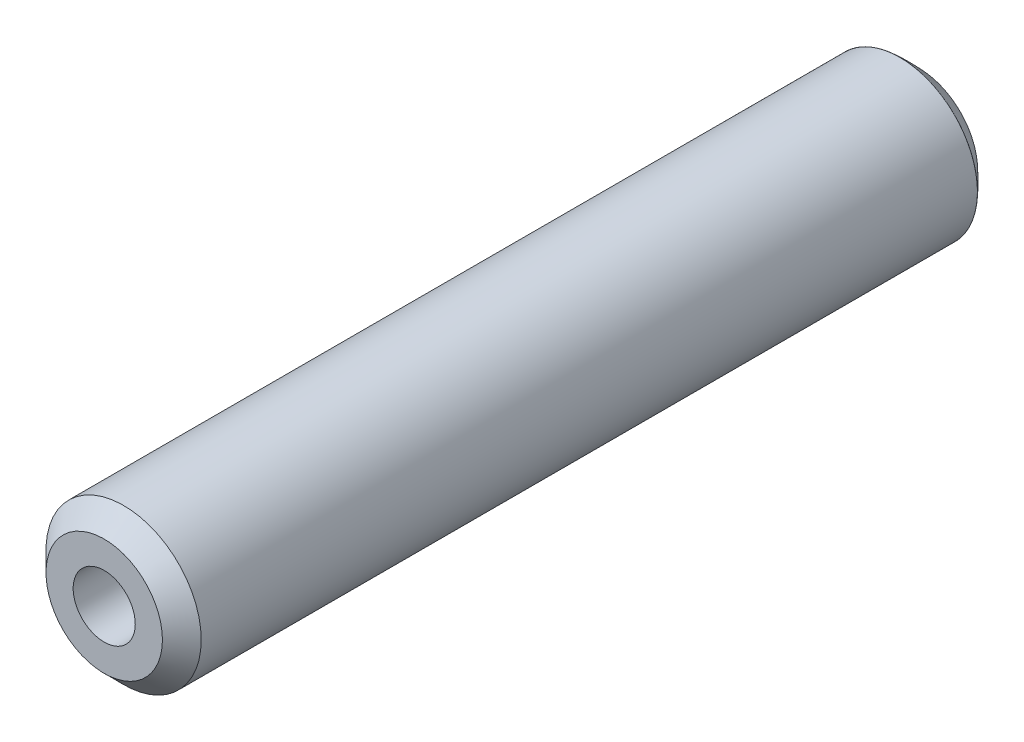
SolidWorks part; units mm, degrees
material "2A12"
ref_plane "前视基准面" through (0, 0, 0) normal (0, 0, 1) x (1, 0, 0)
ref_plane "上视基准面" through (0, 0, 0) normal (0, 1, 0) x (1, 0, 0)
ref_plane "右视基准面" through (0, 0, 0) normal (1, 0, 0) x (0, 0, -1)
sketch "草图2" plane through (0, 0, 0) normal (0, 0, 1) x (1, 0, 0)
  line L0 (0, 19.5) -> (0, -19.5) construction
  line L1 (-19, 19.5) -> (19, 19.5)
  line L2 (-19, 19.5) -> (-19, -19.5)
  line L3 (-19, -19.5) -> (19, -19.5)
  line L4 (19, 19.5) -> (19, -19.5)
  dimension "D1" = 38
  dimension "D2" = 39
extrude "拉伸1" add sketch "草图2" along normal blind 2
sketch "草图3" plane through (0, 0, 2) normal (0, 0, 1) x (1, 0, 0)
  line L0 (-14, 16.5) -> (-14, -16.5) construction
  line L1 (0, 0) -> (-14, 0) construction
  line L2 (-19, 19.5) -> (-19, -19.5) construction
  circle A0 centre (-14, 16.5) radius 1.75
  circle A1 centre (-14, -16.5) radius 1.75
  dimension "D2" = 3.5
  dimension "D1" = 33
  dimension "D3" = 5
chamfer "倒角2" [suppressed] distance 22 angle 30
chamfer "倒角3" distance 1 angle 45 2 edges at (-19, -19.5, 1) (-19, 19.5, 1)
sketch "草图4" plane through (0, 0, 2) normal (0, 0, 1) x (1, 0, 0)
  line L0 (8.205, 5.2066) -> (-4.205, -5.2066) construction
  line L1 (2, 0) -> (2, 7.25) construction
  line L2 (-3.5538, 4.6602) -> (7.5538, -4.6602) construction
  line L3 (2, 0) -> (19, 0) construction
  line L4 (-19, 18.5) -> (-19, -18.5) construction
  line L5 (19, -19.5) -> (19, 19.5) construction
  circle A0 centre (2, 0) radius 8.1 construction
  circle A1 centre (2, 0) radius 7.25 construction
  dimension "D1" = 16.2
  dimension "D2" = 14.5
  dimension "D3" = 50
  dimension "D4" = 50
  dimension "D5" = 21
hole_wizard "M1.6 螺纹孔1" [suppressed] positions "3D草图2" profile "草图6" tap size "M1.6" standard "GB"
sketch3d "3D草图2"
  point P3 (13.145, 5.2066, 2)
  point P6 (12.4938, -4.6602, 2)
  point P9 (0.735, -5.2066, 2)
  point P12 (1.3862, 4.6602, 2)
sketch "草图6" plane through (13.145, 5.2066, 2) normal (1, 0, 0) x (0, -1, 0)
  line L0 (0, 0) -> (0, 4.6255)
  line L1 (0, 4.6255) -> (0.625, 4.25)
  line L2 (0.625, 4.25) -> (0.625, 0)
  line L5 (0.625, 0) -> (0, 0)
  line L10 (0, 4.6255) -> (-0.625, 4.25) construction
  line L11 (0, -6.35) -> (0, 107.95) construction
  dimension "螺纹孔钻头直径" = 1.25
  dimension "螺纹孔钻头深度" = 4.25
  dimension "导头角度" = 118
cosmetic thread "Hole Thread1" [suppressed] parameters "D1"=2, "D2"=1.6
cosmetic thread "Hole Thread2" [suppressed] parameters "D1"=2, "D2"=1.6
cosmetic thread "Hole Thread3" [suppressed] parameters "D1"=2, "D2"=1.6
cosmetic thread "Hole Thread4" [suppressed] parameters "D1"=2, "D2"=1.6
sketch "草图7" plane through (0, 0, 2) normal (0, 0, 1) x (1, 0, 0)
  line L0 (-2.25, 0) -> (2, 0) construction
  circle A0 centre (2, 0) radius 4.25
  dimension "D1" = 8.5
extrude "拉伸3" cut sketch "草图7" against normal blind 10
sketch "草图8" plane through (0, 0, 2) normal (0, 0, 1) x (1, 0, 0)
  line L0 (19, 19.5) -> (-18, 19.5) construction
  line L1 (-17, 19.5) -> (-19, 19.5)
  line L2 (-17, 19.5) -> (-17, -19.5)
  line L3 (-17, -19.5) -> (-19, -19.5)
  line L4 (-19, 19.5) -> (-19, -19.5)
  line L5 (-18, -19.5) -> (19, -19.5) construction
  line L6 (-19, 18.5) -> (-19, -18.5) construction
  dimension "D1" = 2
extrude "拉伸4" cut sketch "草图8" against normal blind 10
chamfer "倒角4" [suppressed] distance 1.5 angle 45
fillet "圆角3" radius 2 2 edges at (-17, -19.5, 1) (-17, 19.5, 1)
sketch "Sketch1" plane through (0, 0, 2) normal (0, 0, 1) x (1, 0, 0)
  line L0 (2, 0) -> (19, 0)
  line L1 (19, -19.5) -> (19, 19.5) construction
  line L2 (7.7569, 7.557) -> (-3.7569, -7.557)
  line L3 (-3.7569, 7.557) -> (7.7569, -7.557)
  dimension "D1" = 52.7
  dimension "D2" = 19
  dimension "D3" = 52.7
hole_wizard "M2.5 Tapped Hole1" [suppressed] positions "3DSketch1" profile "Sketch2" tap size "M2.5" standard "GB"
sketch3d "3DSketch1"
  point P0 (-3.7569, -7.557, 2)
  point P3 (7.7569, 7.557, 2)
  point P7 (-3.7569, 7.557, 2)
  point P10 (7.7569, -7.557, 2)
sketch "Sketch2" plane through (-3.7569, -7.557, 2) normal (1, 0, 0) x (0, -1, 0)
  line L0 (0, 0) -> (0, 7.8659)
  line L1 (0, 7.8659) -> (1.025, 7.25)
  line L2 (1.025, 7.25) -> (1.025, 0)
  line L5 (1.025, 0) -> (0, 0)
  line L10 (0, 7.8659) -> (-1.025, 7.25) construction
  line L11 (0, -6.35) -> (0, 107.95) construction
  dimension "Tap Drill Dia." = 2.05
  dimension "Tap Drill Depth" = 7.25
  dimension "Drill Angle" = 118
cosmetic thread "Hole Thread5" [suppressed] parameters "D1"=2, "D2"=2.5
cosmetic thread "Hole Thread6" [suppressed] parameters "D1"=2, "D2"=2.5
cosmetic thread "Hole Thread7" [suppressed] parameters "D1"=2, "D2"=2.5
cosmetic thread "Hole Thread8" [suppressed] parameters "D1"=2, "D2"=2.5
fillet "Fillet1" [suppressed] radius 3
sketch "Sketch3" [suppressed] plane through (0, 0, 2) normal (0, 0, 1) x (1, 0, 0)
  line L1 (19, 19.5) -> (15, 19.5)
  line L2 (19, 19.5) -> (19, 9.5)
  line L3 (19, 9.5) -> (15, 9.5)
  line L4 (15, 19.5) -> (15, 9.5)
  line L5 (19, -19.5) -> (15, -19.5)
  line L6 (19, -19.5) -> (19, -9.5)
  line L7 (19, -9.5) -> (15, -9.5)
  line L8 (15, -19.5) -> (15, -9.5)
  dimension "D1" = 10
  dimension "D2" = 4
extrude "Extrude1" [suppressed] cut sketch "Sketch3" against normal blind 10
chamfer "Chamfer1" [suppressed] distance 5 angle 45
fillet "Fillet2" [suppressed] radius 2.5
fillet "Fillet3" [suppressed] radius 2.5
fillet "Fillet4" [suppressed] radius 2.5
chamfer "Chamfer2" [suppressed] distance 4 angle 45
sketch "草图9" plane through (0, 0, 2) normal (0, 0, 1) x (1, 0, 0)
  circle A0 centre (-15, 17.5) radius 2
  arc A2 (-15, 19.5) -> (-17, 17.5) centre (-15, 17.5) ccw construction
  circle A3 centre (-15, -17.5) radius 2
  arc A4 (-17, -17.5) -> (-15, -19.5) centre (-15, -17.5) ccw construction
extrude "凸台-拉伸1" add sketch "草图9" along normal blind 21
mirror "镜向1" about plane through (0, 0, 0) normal (0, 1, 0) of "凸台-拉伸1"
fillet "圆角4" [suppressed] radius 1.5
sketch "草图10" plane through (0, 0, 0) normal (0, 0, -1) x (-1, 0, 0)
  line L0 (15, -19.5) -> (-19, -19.5) construction
  line L1 (-19, 19.5) -> (-16, 19.5)
  line L2 (-19, 19.5) -> (-19, -19.5)
  line L3 (-19, -19.5) -> (-16, -19.5)
  line L4 (-16, 19.5) -> (-16, -19.5)
  dimension "D1" = 3
extrude "切除-拉伸1" cut sketch "草图10" against normal blind 10
fillet "圆角5" radius 2 2 edges at (16, -19.5, 1) (16, 19.5, 1)
chamfer "倒角5" distance 0.5 angle 45 10 edges at (-13, -17.5, 23) (-13, 17.5, 23) (15.4142, 18.9142, 0) (16, 0, 0) (-0.5, 19.5, 0) (15.4142, -18.9142, 0) (-16.4142, 18.9142, 0) (-0.5, -19.5, 0) (-17, 0, 0) (-16.4142, -18.9142, 0)
sketch "草图20" plane through (0, 0, 0) normal (0, 0, -1) x (-1, 0, 0)
  line L0 (3.7569, 7.557) -> (-7.7569, -7.557) construction
  line L1 (-9.5, -15.5) -> (5.5, -15.5)
  line L2 (-9.5, -15.5) -> (-9.5, 15.5)
  line L3 (-9.5, 15.5) -> (5.5, 15.5)
  line L4 (5.5, -15.5) -> (5.5, 15.5)
  line L5 (-9.5, -15.5) -> (5.5, 15.5) construction
  line L6 (-9.5, 15.5) -> (5.5, -15.5) construction
  line L7 (-14, 19.5) -> (15, 19.5) construction
  point P0 (-2, 0)
  dimension "D1" = 4
  dimension "D2" = 15
hole_wizard "M2.5 螺纹孔3" positions "3D草图7" profile "草图21" tap size "M2.5" standard "GB" end condition up to next
sketch3d "3D草图7"
  point P0 (9.5, 15.5, 0)
  point P3 (-5.5, 15.5, 0)
  point P6 (9.5, -15.5, 0)
  point P9 (-5.5, -15.5, 0)
sketch "草图21" plane through (9.5, 15.5, 0) normal (1, 0, 0) x (0, 1, 0)
  line L0 (0, 0) -> (0, 2)
  line L1 (0, 2) -> (1.025, 2)
  line L2 (1.025, 2) -> (1.025, 0)
  line L5 (1.025, 0) -> (0, 0)
  line L11 (0, -6.35) -> (0, 107.95) construction
  dimension "通孔螺纹孔钻头直径" = 2.05
  dimension "通孔螺纹孔钻头深度" = 2
cosmetic thread "孔螺蚊线7" parameters "D2"=2.5
cosmetic thread "孔螺蚊线8" parameters "D2"=2.5
cosmetic thread "孔螺蚊线9" parameters "D2"=2.5
cosmetic thread "孔螺蚊线10" parameters "D2"=2.5
hole_wizard "M2 螺纹孔1" positions "3D草图8" profile "草图22" tap size "M2" standard "GB"
sketch3d "3D草图8"
  line L0 (-15, 17.5, 22.5) -> (-15, 17.5, 23) construction
  line L1 (-15, -17.5, 22.5) -> (-15, -17.5, 23) construction
  point P0 (-15, 17.5, 23)
  point P4 (-15, -17.5, 23)
cosmetic thread "孔螺蚊线11" parameters "D1"=5, "D2"=2
cosmetic thread "孔螺蚊线12" parameters "D1"=5, "D2"=2
sketch "草图22" plane through (-15, 17.5, 23) normal (1, 0, 0) x (0, -1, 0)
  line L0 (0, 0) -> (0, 7.4807)
  line L1 (0, 7.4807) -> (0.8, 7)
  line L2 (0.8, 7) -> (0.8, 0)
  line L5 (0.8, 0) -> (0, 0)
  line L10 (0, 7.4807) -> (-0.8, 7) construction
  line L11 (0, -6.35) -> (0, 107.95) construction
  dimension "螺纹孔钻头直径" = 1.6
  dimension "螺纹孔钻头深度" = 7
  dimension "导头角度" = 118
sketch "草图23" plane through (0, 0, 0) normal (0, 0, -1) x (-1, 0, 0)
  line L0 (-2, 16.2) -> (-2, 9.8) construction
  line L1 (-0.95, 16.2) -> (-0.95, 9.8)
  line L2 (-3.05, 16.2) -> (-3.05, 9.8)
  line L3 (-14, 19.5) -> (15, 19.5) construction
  line L4 (-16, -17.5) -> (-16, 17.5) construction
  arc A0 (-0.95, 16.2) -> (-3.05, 16.2) centre (-2, 16.2) ccw
  arc A1 (-3.05, 9.8) -> (-0.95, 9.8) centre (-2, 9.8) ccw
  point P2 (-2, 13)
  dimension "D1" = 1.05
  dimension "D2" = 3.3
  dimension "D3" = 14
  dimension "D4" = 6.4
extrude "切除-拉伸2" cut sketch "草图23" against normal blind 10
mirror "镜向2" about plane through (0, 0, 0) normal (0, 1, 0) of "切除-拉伸2"
sketch "草图24" plane through (0, 0, 2) normal (0, 0, 1) x (1, 0, 0)
  line L1 (35.6453, -25.5723) -> (-35.6453, -25.5723)
  line L2 (35.6453, -25.5723) -> (35.6453, 25.5723)
  line L3 (35.6453, 25.5723) -> (-35.6453, 25.5723)
  line L4 (-35.6453, -25.5723) -> (-35.6453, 25.5723)
  line L5 (35.6453, -25.5723) -> (-35.6453, 25.5723) construction
  line L6 (35.6453, 25.5723) -> (-35.6453, -25.5723) construction
  point P0 (0, 0)
extrude "切除-拉伸3" cut sketch "草图24" against normal blind 10
sketch "草图25" plane through (0, 0, 2) normal (0, 0, -1) x (-1, 0, 0)
  circle A0 centre (15, 17.5) radius 6.5393
extrude "切除-拉伸4" cut sketch "草图25" against normal blind 32
hole_wizard "M2 螺纹孔2" positions "3D草图9" profile "草图26" tap size "M2" standard "GB"
sketch3d "3D草图9"
  line L0 (-15, -17.5, 2) -> (-15, -17.5, 22.5) construction
  point P0 (-15, -17.5, 2)
sketch "草图26" plane through (-15, -17.5, 2) normal (1, 0, 0) x (0, 1, 0)
  line L0 (0, 0) -> (0, 7.4807)
  line L1 (0, 7.4807) -> (0.8, 7)
  line L2 (0.8, 7) -> (0.8, 0)
  line L5 (0.8, 0) -> (0, 0)
  line L10 (0, 7.4807) -> (-0.8, 7) construction
  line L11 (0, -6.35) -> (0, 107.95) construction
  dimension "螺纹孔钻头直径" = 1.6
  dimension "螺纹孔钻头深度" = 7
  dimension "导头角度" = 118
cosmetic thread "孔螺蚊线13" parameters "D1"=5, "D2"=2
fillet "圆角6" radius 0.5 1 edges at (-13, -17.5, 2)
